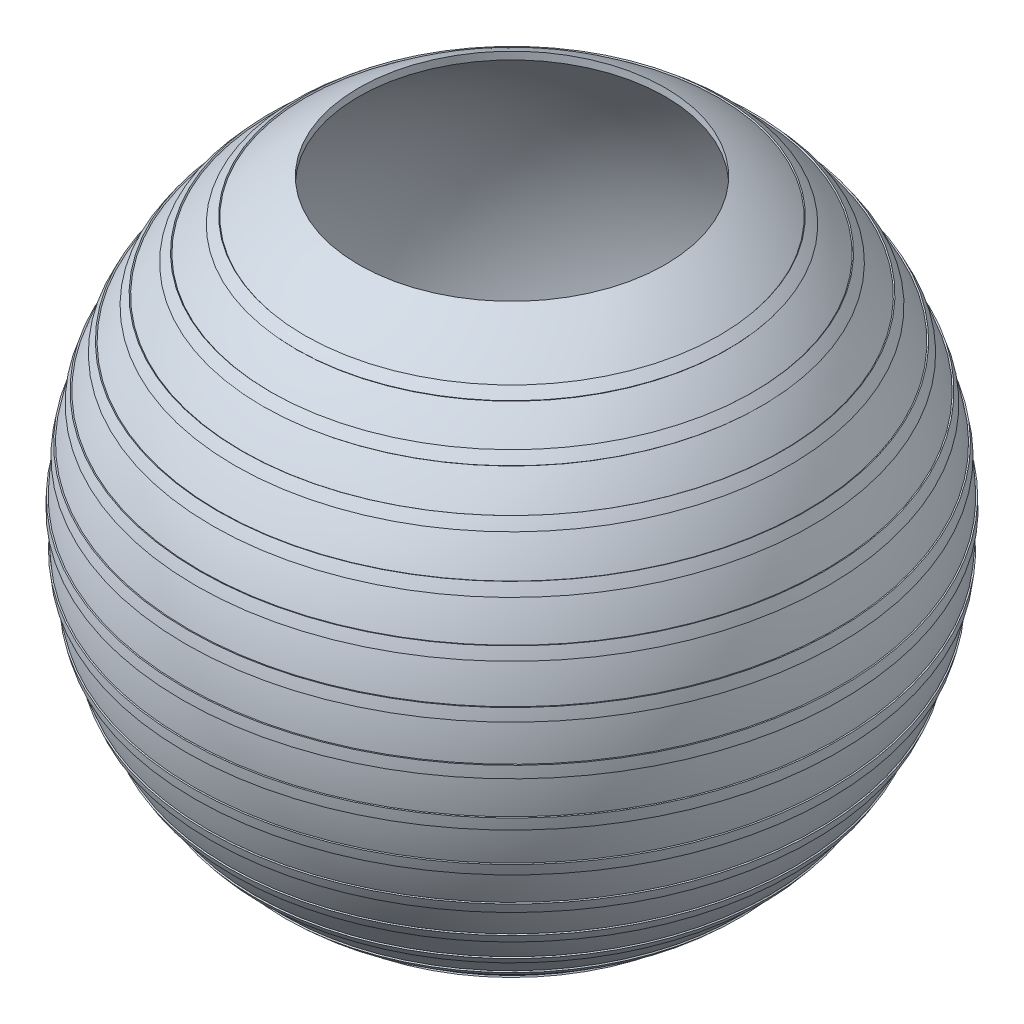
SolidWorks part; units mm, degrees
ref_plane "Alzado" through (0, 0, 0) normal (0, 0, 1) x (1, 0, 0)
ref_plane "Planta" through (0, 0, 0) normal (0, 1, 0) x (1, 0, 0)
ref_plane "Vista lateral" through (0, 0, 0) normal (1, 0, 0) x (0, 0, -1)
sketch "Croquis1" plane through (0, 0, 0) normal (1, 0, 0) x (0, 0, -1)
  line L0 (0, 20.75) -> (0, -24.5) construction
  line L1 (-0.5, 24.4949) -> (-0.5, 23.9948)
  line L2 (0, -24) -> (0, -24.5)
  arc A0 (-0.5, 24.4949) -> (0, -24.5) centre (0, 0) ccw
  arc A1 (-0.5, 23.9948) -> (0, -24) centre (0, 0) ccw
  dimension "D1" = 48
  dimension "D2" = 49
  dimension "D3" = 0.5
revolve "Revolución1" add sketch "Croquis1" angle 360 about L0
sketch "Croquis2" plane through (0, 0, 0) normal (1, 0, 0) x (0, 0, -1)
  line L0 (0, 0) -> (0, 34.8833) construction
  line L2 (0, 13.6121) -> (0, 24.5)
  line L3 (11.4374, 21.6665) -> (11.4374, 13.6121)
  line L4 (11.4374, 13.6121) -> (0, 13.6121)
  line L5 (0, 0) -> (0, 13.6121) construction
  arc A1 (0, 24.5) -> (11.4374, 21.6665) centre (0, 0) cw
  arc A2 (-0.5, 24.4949) -> (0.5, 24.4949) centre (0, 0) ccw construction
  dimension "D2" = 11.4374
revolve "Cortar-Revolución1" cut sketch "Croquis2" angle 360 about L0
sketch "Croquis3" plane through (0, 0, 0) normal (1, 0, 0) x (0, 0, -1)
  line L0 (-15.4183, 19.0401) -> (-15.4813, 19.1178)
  line L1 (-16.0734, 18.4904) -> (-16.1391, 18.5659)
  line L2 (0, 0) -> (0, 45.5136) construction
  line L3 (0, 0) -> (-15.4183, 19.0401) construction
  line L4 (0, 0) -> (-16.0734, 18.4904) construction
  line L25 (-15.8126, 18.8447) -> (0, 0) construction
  line L52 (-17.9546, 16.6698) -> (-18.0279, 16.7379)
  line L53 (-18.5254, 16.0331) -> (-18.601, 16.0985)
  line L54 (-20.1303, 13.9649) -> (-20.2125, 14.0219)
  line L55 (-20.6055, 13.2539) -> (-20.6896, 13.308)
  line L56 (-21.902, 10.9797) -> (-21.9914, 11.0245)
  line L57 (-22.2718, 10.2086) -> (-22.3627, 10.2503)
  line L58 (-23.2339, 7.774) -> (-23.3288, 7.8057)
  line L59 (-23.4911, 6.9584) -> (-23.587, 6.9868)
  line L60 (-24.0994, 4.4122) -> (-24.1978, 4.4302)
  line L61 (-24.2387, 3.5685) -> (-24.3377, 3.583)
  line L62 (-24.4811, 0.9619) -> (-24.581, 0.9658)
  line L63 (-24.4998, 0.1069) -> (-24.5998, 0.1073)
  line L64 (-24.3713, -2.5078) -> (-24.4708, -2.518)
  line L65 (-24.2689, -3.3568) -> (-24.368, -3.3705)
  line L66 (-23.7722, -5.9271) -> (-23.8693, -5.9513)
  line L67 (-23.5509, -6.7531) -> (-23.647, -6.7807)
  line L68 (-22.6959, -9.2274) -> (-22.7886, -9.2651)
  line L69 (-22.3601, -10.0139) -> (-22.4513, -10.0547)
  line L70 (-21.164, -12.3425) -> (-21.2504, -12.3928)
  line L71 (-20.7203, -13.0736) -> (-20.8049, -13.1269)
  line L72 (-19.2071, -15.2097) -> (-19.2855, -15.2718)
  line L73 (-18.6646, -15.8708) -> (-18.7408, -15.9356)
  line L74 (-16.8647, -17.7717) -> (-16.9335, -17.8442)
  line L75 (-16.2342, -18.3494) -> (-16.3005, -18.4243)
  line L76 (-14.1837, -19.9768) -> (-14.2416, -20.0584)
  line L77 (-13.4779, -20.4597) -> (-13.5329, -20.5432)
  line L78 (-11.2179, -21.7809) -> (-11.2637, -21.8698)
  line L79 (-10.4509, -22.1592) -> (-10.4936, -22.2496)
  line L80 (-8.0269, -23.1477) -> (-8.0597, -23.2422)
  line L81 (-7.2142, -23.4138) -> (-7.2437, -23.5093)
  line L82 (-4.6748, -24.0499) -> (-4.6939, -24.148)
  line L83 (-3.8326, -24.1984) -> (-3.8483, -24.2971)
  line L84 (0, 0) -> (-15.4183, 19.0401) construction
  arc A0 (-15.4183, 19.0401) -> (-16.0734, 18.4904) centre (0, 0) ccw
  arc A1 (-15.4813, 19.1178) -> (-16.1391, 18.5659) centre (0, 0) ccw
  arc A2 (-16.0734, 18.4904) -> (0, 24.5) centre (0, 0) ccw construction
  arc A3 (0, 24.5) -> (-15.4183, 19.0401) centre (0, 0) ccw construction
  arc A4 (0, 24.6) -> (-15.4813, 19.1178) centre (0, 0) ccw construction
  arc A5 (-16.1391, 18.5659) -> (0, 24.6) centre (0, 0) ccw construction
  arc A36 (-17.9546, 16.6698) -> (-18.5254, 16.0331) centre (0, 0) ccw
  arc A37 (-18.0279, 16.7379) -> (-18.601, 16.0985) centre (0, 0) ccw
  arc A38 (-20.1303, 13.9649) -> (-20.6055, 13.2539) centre (0, 0) ccw
  arc A39 (-20.2125, 14.0219) -> (-20.6896, 13.308) centre (0, 0) ccw
  arc A40 (-21.902, 10.9797) -> (-22.2718, 10.2086) centre (0, 0) ccw
  arc A41 (-21.9914, 11.0245) -> (-22.3627, 10.2503) centre (0, 0) ccw
  arc A42 (-23.2339, 7.774) -> (-23.4911, 6.9584) centre (0, 0) ccw
  arc A43 (-23.3288, 7.8057) -> (-23.587, 6.9868) centre (0, 0) ccw
  arc A44 (-24.0994, 4.4122) -> (-24.2387, 3.5685) centre (0, 0) ccw
  arc A45 (-24.1978, 4.4302) -> (-24.3377, 3.583) centre (0, 0) ccw
  arc A46 (-24.4811, 0.9619) -> (-24.4998, 0.1069) centre (0, 0) ccw
  arc A47 (-24.581, 0.9658) -> (-24.5998, 0.1073) centre (0, 0) ccw
  arc A48 (-24.3713, -2.5078) -> (-24.2689, -3.3568) centre (0, 0) ccw
  arc A49 (-24.4708, -2.518) -> (-24.368, -3.3705) centre (0, 0) ccw
  arc A50 (-23.7722, -5.9271) -> (-23.5509, -6.7531) centre (0, 0) ccw
  arc A51 (-23.8693, -5.9513) -> (-23.647, -6.7807) centre (0, 0) ccw
  arc A52 (-22.6959, -9.2274) -> (-22.3601, -10.0139) centre (0, 0) ccw
  arc A53 (-22.7886, -9.2651) -> (-22.4513, -10.0547) centre (0, 0) ccw
  arc A54 (-21.164, -12.3425) -> (-20.7203, -13.0736) centre (0, 0) ccw
  arc A55 (-21.2504, -12.3928) -> (-20.8049, -13.1269) centre (0, 0) ccw
  arc A56 (-19.2071, -15.2097) -> (-18.6646, -15.8708) centre (0, 0) ccw
  arc A57 (-19.2855, -15.2718) -> (-18.7408, -15.9356) centre (0, 0) ccw
  arc A58 (-16.8647, -17.7717) -> (-16.2342, -18.3494) centre (0, 0) ccw
  arc A59 (-16.9335, -17.8442) -> (-16.3005, -18.4243) centre (0, 0) ccw
  arc A60 (-14.1837, -19.9768) -> (-13.4779, -20.4597) centre (0, 0) ccw
  arc A61 (-14.2416, -20.0584) -> (-13.5329, -20.5432) centre (0, 0) ccw
  arc A62 (-11.2179, -21.7809) -> (-10.4509, -22.1592) centre (0, 0) ccw
  arc A63 (-11.2637, -21.8698) -> (-10.4936, -22.2496) centre (0, 0) ccw
  arc A64 (-8.0269, -23.1477) -> (-7.2142, -23.4138) centre (0, 0) ccw
  arc A65 (-8.0597, -23.2422) -> (-7.2437, -23.5093) centre (0, 0) ccw
  arc A66 (-4.6748, -24.0499) -> (-3.8326, -24.1984) centre (0, 0) ccw
  arc A67 (-4.6939, -24.148) -> (-3.8483, -24.2971) centre (0, 0) ccw
  point P33 (0, 0)
  dimension "D1" = 17
  dimension "D2" = 49.2
  dimension "D3" = 40
  dimension "D4" = 24.5
  dimension "D5" = 0.8552
revolve "Revolución2" add sketch "Croquis3" angle 360 about L2
ref_plane "Plano1" [suppressed] through (0, 1.2306, 20.7135) normal (0, 0.0593, 0.9982) x (1, 0, 0)
sketch "Croquis4" [suppressed] plane through (0, 1.2306, 20.7135) normal (0, 0.0593, 0.9982) x (1, 0, 0)
  circle A0 centre (0, 0) radius 0.75
  dimension "D1" = 1.5
extrude "Cortar-Extruir1" [suppressed] cut sketch "Croquis4" against normal blind 4
ref_axis "Eje1" through (23.1, 0, 0) along (-1, 0, 0)
ref_axis "Eje2" through (0, 19.3158, 0) along (0, -1, 0)
pattern_circular "MatrizC1" [suppressed] count 2 every 21.7 about axis through (23.1, 0, 0) along (-1, 0, 0) other way count 4 other way every 21.7 of bodies 104
pattern_circular "MatrizC2" [suppressed] count 8 over 360 about axis through (0, 19.3158, 0) along (0, -1, 0) of bodies 105
pattern_circular "MatrizC3" [suppressed] count 4 over 360 about axis through (0, 19.3158, 0) along (0, -1, 0) of bodies 106
ref_plane "Plano2" through (0, -24.5, 0) normal (0, -1, 0) x (-1, 0, 0)
sketch "Croquis5" plane through (0, -24.5, 0) normal (0, -1, 0) x (-1, 0, 0)
  circle A0 centre (0, 0) radius 7.5
  circle A1 centre (0, 0) radius 10
  circle A2 centre (0, 0) radius 17.5
  circle A3 centre (0, 0) radius 12.5
  circle A4 centre (0, 0) radius 12.5336
  circle A5 centre (0, 0) radius 15
  dimension "D1" = 15
  dimension "D2" = 20
  dimension "D3" = 25
  dimension "D4" = 35
  dimension "D5" = 30
extrude "Extruir-Lámina1" [suppressed] add sketch "Croquis5" against normal up to surface (9.742 mm away) thin contours A2 | A5 | A3 | A1 | A0 thin type one direction wall 0.5
